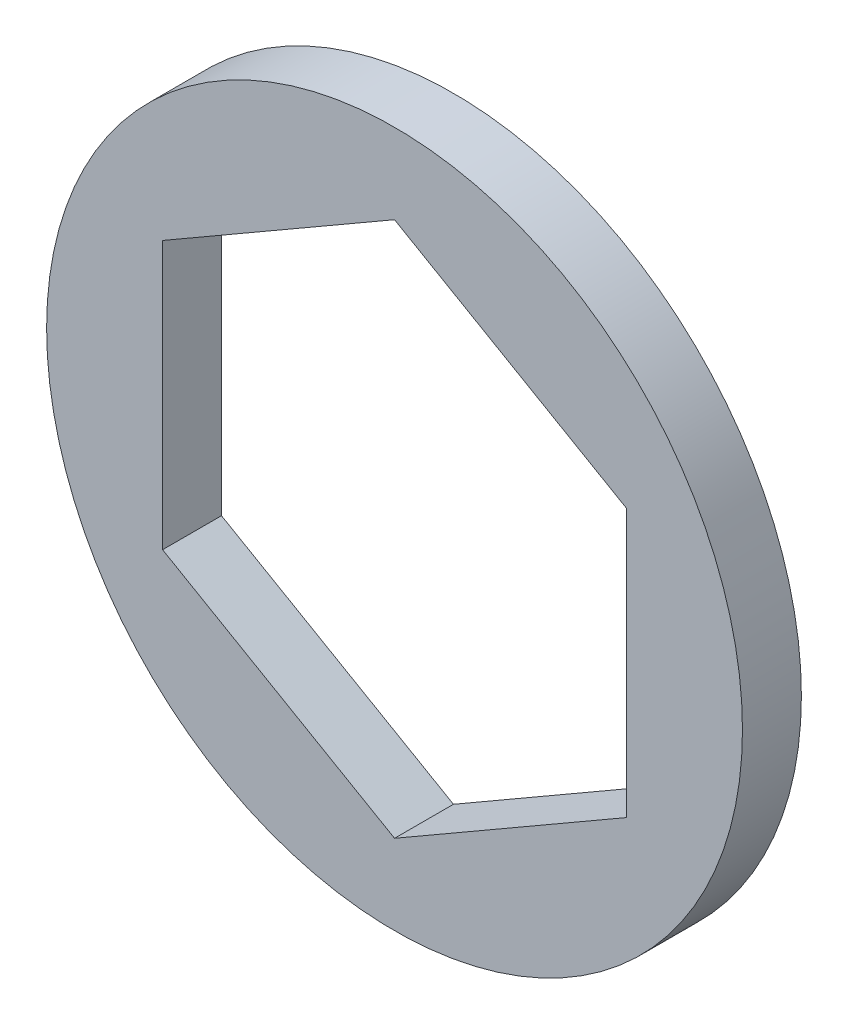
SolidWorks part; units mm, degrees
material "Nylon 101"
ref_plane "Front Plane" through (0, 0, 0) normal (0, 0, 1) x (1, 0, 0)
ref_plane "Top Plane" through (0, 0, 0) normal (0, 1, 0) x (1, 0, 0)
ref_plane "Right Plane" through (0, 0, 0) normal (1, 0, 0) x (0, 0, -1)
sketch "Sketch1" plane through (0, 0, 0) normal (0, 0, 1) x (1, 0, 0)
  line L1 (0, 7.3323) -> (-6.35, 3.6662)
  line L2 (-6.35, 3.6662) -> (-6.35, -3.6662)
  line L3 (-6.35, -3.6662) -> (0, -7.3323)
  line L4 (0, -7.3323) -> (6.35, -3.6662)
  line L5 (6.35, -3.6662) -> (6.35, 3.6662)
  line L6 (6.35, 3.6662) -> (0, 7.3323)
  circle A0 centre (0, 0) radius 9.525
  circle A1 centre (0, 0) radius 6.35 construction
  dimension "D1" = 12.7
  dimension "D2" = 19.05
extrude "Boss-Extrude1" add sketch "Sketch1" along normal blind 1.6129
